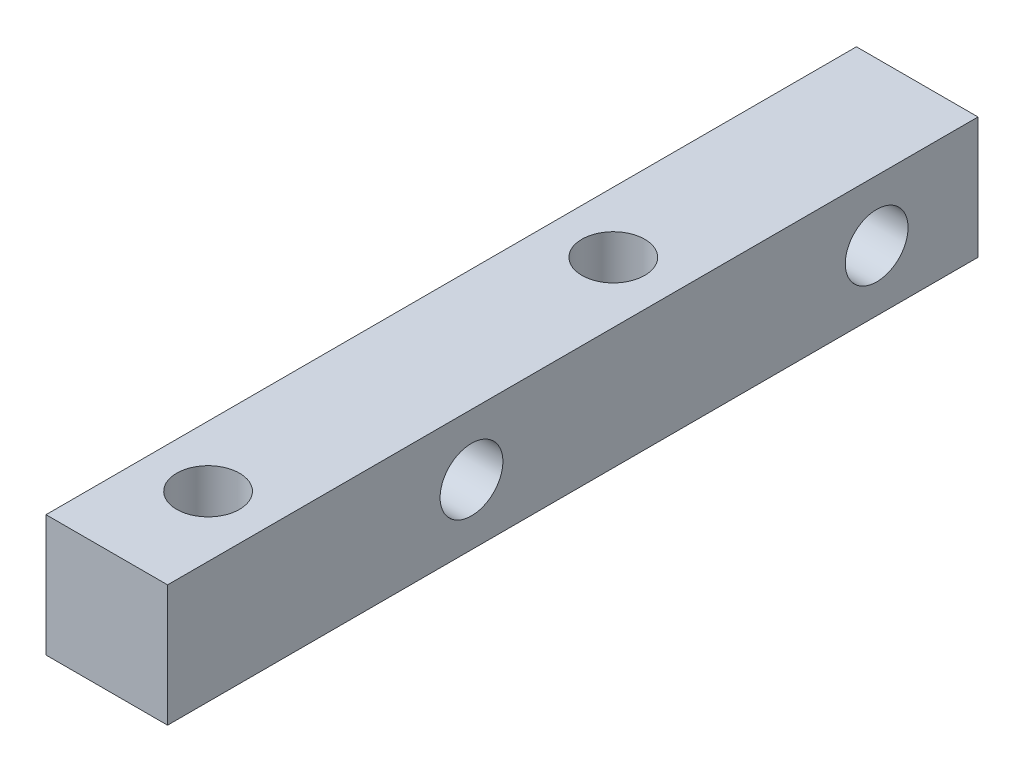
SolidWorks part; units mm, degrees
material "7050-T73510"
ref_plane "前视基准面" through (0, 0, 0) normal (0, 0, 1) x (1, 0, 0)
ref_plane "上视基准面" through (0, 0, 0) normal (0, 1, 0) x (1, 0, 0)
ref_plane "右视基准面" through (0, 0, 0) normal (1, 0, 0) x (0, 0, -1)
sketch "草图2" plane through (0, 0, 0) normal (0, 0, 1) x (1, 0, 0)
  line L1 (0, 0) -> (6, 0)
  line L2 (0, 0) -> (0, 6)
  line L3 (0, 6) -> (6, 6)
  line L4 (6, 0) -> (6, 6)
  dimension "D1" = 6
  dimension "D2" = 6
extrude "凸台-拉伸1" add sketch "草图2" along normal blind 40
sketch "草图3" plane through (0, 6, 0) normal (0, 1, 0) x (1, 0, 0)
  line L0 (3, -40) -> (3, -35) construction
  line L1 (6, -40) -> (0, -40) construction
  line L2 (3, -35) -> (3, -15)
  circle A0 centre (3, -35) radius 1.55
  circle A1 centre (3, -15) radius 1.55
  dimension "D2" = 3.1
  dimension "D4" = 3.1
  dimension "D1" = 5
  dimension "D3" = 20
extrude "切除-拉伸1" cut sketch "草图3" against normal blind 40 contours A1 | A0 L0 L2 | L0 A0 L2 region at (2.3422, 6, 35) region at (1.935, 6, 13.935) region at (3.6578, 6, 35)
sketch "草图4" plane through (0, 0, 0) normal (-1, 0, 0) x (0, 0, 1)
  line L0 (0, 3) -> (5, 3) construction
  line L1 (0, 6) -> (0, 0) construction
  line L2 (5, 3) -> (25, 3) construction
  circle A0 centre (5, 3) radius 1.55
  circle A1 centre (25, 3) radius 1.55
  dimension "D2" = 3.1
  dimension "D4" = 3.1
  dimension "D1" = 5
  dimension "D3" = 20
extrude "切除-拉伸2" cut sketch "草图4" against normal blind 40 contours A0 | A1
